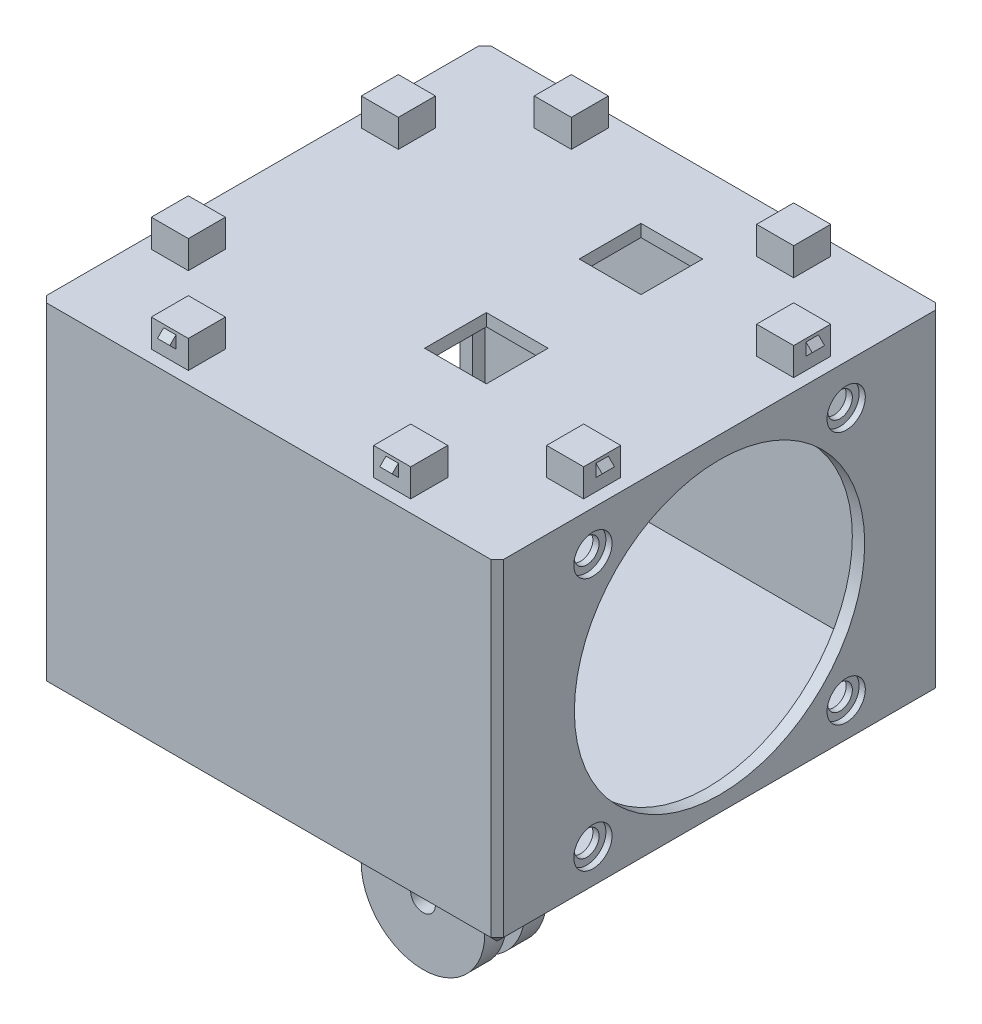
SolidWorks part; units mm, degrees
ref_plane "前视基准面" through (0, 0, 0) normal (0, 0, 1) x (1, 0, 0)
ref_plane "上视基准面" through (0, 0, 0) normal (0, 1, 0) x (1, 0, 0)
ref_plane "右视基准面" through (0, 0, 0) normal (1, 0, 0) x (0, 0, -1)
sketch "草图1" plane through (0, 0, 0) normal (0, 1, 0) x (1, 0, 0)
  line L1 (-65.7153, 32.1762) -> (8.2847, 32.1762)
  line L2 (-65.7153, 32.1762) -> (-65.7153, -39.8238)
  line L3 (-65.7153, -39.8238) -> (8.2847, -39.8238)
  line L4 (8.2847, 32.1762) -> (8.2847, -39.8238)
  dimension "D1" = 74
  dimension "D5" = 72
extrude "凸台-拉伸1" add sketch "草图1" along normal blind 54
sketch "草图2" plane through (0, 54, 0) normal (0, 1, 0) x (1, 0, 0)
  line L0 (8.2847, -39.8238) -> (8.2847, 32.1762) construction
  line L1 (6.2847, 30.1762) -> (-63.7153, 30.1762)
  line L2 (6.2847, 30.1762) -> (6.2847, -37.8238)
  line L3 (6.2847, -37.8238) -> (-63.7153, -37.8238)
  line L4 (-63.7153, 30.1762) -> (-63.7153, -37.8238)
  line L5 (-65.7153, -39.8238) -> (8.2847, -39.8238) construction
  line L6 (8.2847, 32.1762) -> (-65.7153, 32.1762) construction
  line L7 (-65.7153, 32.1762) -> (-65.7153, -39.8238) construction
  dimension "D1" = 2
  dimension "D2" = 2
  dimension "D3" = 2
  dimension "D4" = 2
extrude "切除-拉伸1" cut sketch "草图2" against normal blind 52
sketch "草图4" plane through (8.2847, 0, 0) normal (1, 0, 0) x (0, 0, -1)
  line L1 (32.1762, 54) -> (32.1762, 0) construction
  line L2 (-39.8238, 0) -> (32.1762, 0) construction
  circle A0 centre (-3.8238, 27) radius 23.5
  circle A1 centre (16.6762, 6.5) radius 2
  circle A2 centre (-24.3238, 47.5) radius 2
  circle A3 centre (-24.3238, 6.5) radius 2
  circle A4 centre (16.6762, 47.5) radius 2
  dimension "D1" = 47
  dimension "D2" = 20.5
  dimension "D8" = 4
  dimension "D3" = 20.5
  dimension "D4" = 20.5
  dimension "D5" = 20.5
  dimension "D6" = 36
  dimension "D7" = 27
extrude "切除-拉伸2" cut sketch "草图4" against normal blind 2
sketch "草图5" plane through (0, 0, 0) normal (0, -1, 0) x (1, 0, 0)
  line L0 (-65.7153, -32.1762) -> (-65.7153, 39.8238) construction
  line L1 (-63.7153, 37.8238) -> (-49.7153, 37.8238)
  line L2 (-63.7153, 37.8238) -> (-63.7153, -30.1762)
  line L3 (-63.7153, -30.1762) -> (-49.7153, -30.1762)
  line L4 (-49.7153, 37.8238) -> (-49.7153, -30.1762)
  line L5 (-65.7153, 39.8238) -> (8.2847, 39.8238) construction
  line L6 (8.2847, -32.1762) -> (-65.7153, -32.1762) construction
  dimension "D1" = 2
  dimension "D2" = 2
  dimension "D3" = 2
  dimension "D4" = 14
extrude "切除-拉伸3" cut sketch "草图5" against normal blind 2
sketch "草图6" plane through (0, 0, 37.8238) normal (0, 0, -1) x (-1, 0, 0)
  line L0 (63.7153, 54) -> (-6.2847, 54) construction
  line L1 (63.7153, 52) -> (54.7153, 52)
  line L2 (63.7153, 52) -> (63.7153, 54)
  line L3 (63.7153, 54) -> (54.7153, 54)
  line L4 (54.7153, 52) -> (54.7153, 54)
  line L9 (63.7153, 0) -> (63.7153, 54) construction
  dimension "D1" = 9
  dimension "D2" = 2
  dimension "D3" = 0
  dimension "D4" = 0
sketch "草图7" plane through (0, 0, -30.1762) normal (0, 0, 1) x (1, 0, 0)
  line L0 (-54.7153, 52) -> (-54.7153, 54) construction
  line L1 (-63.7153, 54) -> (-54.7153, 54)
  line L2 (-63.7153, 54) -> (-63.7153, 52)
  line L3 (-63.7153, 52) -> (-54.7153, 52)
  line L4 (-54.7153, 54) -> (-54.7153, 52)
  line L5 (-63.7153, 54) -> (-54.7153, 54) construction
  line L6 (6.2847, 54) -> (-63.7153, 54) construction
  line L7 (-63.7153, 0) -> (-63.7153, 54) construction
  point P12 (-63.7153, 53)
  dimension "D1" = 0
extrude "凸台-拉伸2" add sketch "草图6" along normal blind 5
extrude "凸台-拉伸3" add sketch "草图7" along normal blind 5
sketch "草图9" plane through (-65.7153, 0, 0) normal (-1, 0, 0) x (0, 0, 1)
  line L0 (39.8238, 54) -> (39.8238, 0) construction
  line L1 (35.8238, 50) -> (-28.1762, 50)
  line L2 (35.8238, 50) -> (35.8238, 4)
  line L3 (35.8238, 4) -> (-28.1762, 4)
  line L4 (-28.1762, 50) -> (-28.1762, 4)
  line L5 (-32.1762, 0) -> (39.8238, 0) construction
  line L6 (-32.1762, 54) -> (39.8238, 54) construction
  line L7 (-32.1762, 54) -> (-32.1762, 0) construction
  dimension "D1" = 4
  dimension "D2" = 4
  dimension "D3" = 4
  dimension "D4" = 4
extrude "切除-拉伸4" cut sketch "草图9" against normal up to next
sketch "草图10" plane through (0, 0, 37.8238) normal (0, 0, -1) x (-1, 0, 0)
  line L0 (49.7153, 2) -> (-6.2847, 2) construction
  line L9 (49.7153, 10) -> (45.7153, 10)
  line L10 (49.7153, 10) -> (49.7153, 18)
  line L11 (49.7153, 18) -> (45.7153, 18)
  line L12 (45.7153, 10) -> (45.7153, 18)
  line L13 (49.7153, 25) -> (49.7153, 33)
  line L14 (49.7153, 25) -> (45.7153, 25)
  line L15 (45.7153, 25) -> (45.7153, 33)
  line L16 (49.7153, 33) -> (45.7153, 33)
  line L17 (49.7153, 40) -> (49.7153, 48)
  line L18 (49.7153, 40) -> (45.7153, 40)
  line L19 (45.7153, 40) -> (45.7153, 48)
  line L20 (49.7153, 48) -> (45.7153, 48)
  line L21 (49.7153, 2) -> (49.7153, 0) construction
  point P0 (47.7153, 10)
  dimension "D1" = 4
  dimension "D2" = 8
  dimension "D3" = 8
  dimension "D4" = 3
extrude "凸台-拉伸5" add sketch "草图10" along normal blind 5
sketch "草图11" plane through (0, 0, -30.1762) normal (0, 0, 1) x (1, 0, 0)
  line L0 (6.2847, 2) -> (-49.7153, 2) construction
  line L1 (-45.7153, 10) -> (-49.7153, 10)
  line L2 (-45.7153, 10) -> (-45.7153, 18)
  line L3 (-45.7153, 18) -> (-49.7153, 18)
  line L4 (-49.7153, 10) -> (-49.7153, 18)
  line L5 (-45.7153, 25) -> (-45.7153, 33)
  line L6 (-45.7153, 25) -> (-49.7153, 25)
  line L7 (-49.7153, 25) -> (-49.7153, 33)
  line L8 (-45.7153, 33) -> (-49.7153, 33)
  line L9 (-45.7153, 40) -> (-45.7153, 48)
  line L10 (-45.7153, 40) -> (-49.7153, 40)
  line L11 (-49.7153, 40) -> (-49.7153, 48)
  line L12 (-45.7153, 48) -> (-49.7153, 48)
  line L13 (-49.7153, 2) -> (-49.7153, 0) construction
  dimension "D1" = 4
  dimension "D2" = 8
  dimension "D3" = 8
  dimension "D4" = 3
extrude "凸台-拉伸6" add sketch "草图11" along normal blind 5
sketch "草图15" plane through (0, 54, 0) normal (0, 1, 0) x (1, 0, 0)
  line L0 (6.2847, -37.8238) -> (6.2847, 30.1762) construction
  line L1 (-63.7153, 30.1762) -> (6.2847, 30.1762)
  line L2 (-63.7153, 30.1762) -> (-63.7153, -37.8238)
  line L3 (-63.7153, -37.8238) -> (6.2847, -37.8238)
  line L4 (6.2847, 30.1762) -> (6.2847, -37.8238)
  line L5 (-63.7153, 25.1762) -> (-63.7153, -32.8238) construction
extrude "凸台-拉伸7" add sketch "草图15" against normal blind 2
sketch "草图16" plane through (0, 54, 0) normal (0, 1, 0) x (1, 0, 0)
  line L0 (-43.7153, -31.8238) -> (-49.7153, -31.8238)
  line L1 (-57.7153, 16.1762) -> (-63.7153, 16.1762)
  line L2 (-57.7153, 16.1762) -> (-57.7153, 10.1762)
  line L3 (-57.7153, 10.1762) -> (-63.7153, 10.1762)
  line L4 (-63.7153, 16.1762) -> (-63.7153, 10.1762)
  line L5 (-43.7153, -31.8238) -> (-43.7153, -37.8238)
  line L6 (-43.7153, -37.8238) -> (-49.7153, -37.8238)
  line L7 (-49.7153, -31.8238) -> (-49.7153, -37.8238)
  line L8 (-7.7153, -31.8238) -> (-13.7153, -31.8238)
  line L9 (-7.7153, -31.8238) -> (-7.7153, -37.8238)
  line L10 (-7.7153, -37.8238) -> (-13.7153, -37.8238)
  line L11 (-13.7153, -31.8238) -> (-13.7153, -37.8238)
  line L12 (-43.7153, 30.1762) -> (-49.7153, 30.1762)
  line L13 (-43.7153, 30.1762) -> (-43.7153, 24.1762)
  line L14 (-43.7153, 24.1762) -> (-49.7153, 24.1762)
  line L15 (-49.7153, 30.1762) -> (-49.7153, 24.1762)
  line L16 (-7.7153, 30.1762) -> (-13.7153, 30.1762)
  line L17 (-7.7153, 30.1762) -> (-7.7153, 24.1762)
  line L18 (-7.7153, 24.1762) -> (-13.7153, 24.1762)
  line L19 (-13.7153, 30.1762) -> (-13.7153, 24.1762)
  line L20 (6.2847, 16.1762) -> (0.2847, 16.1762)
  line L21 (6.2847, 16.1762) -> (6.2847, 10.1762)
  line L22 (6.2847, 10.1762) -> (0.2847, 10.1762)
  line L23 (0.2847, 16.1762) -> (0.2847, 10.1762)
  line L24 (6.2847, -17.8238) -> (0.2847, -17.8238)
  line L25 (6.2847, -17.8238) -> (6.2847, -23.8238)
  line L26 (6.2847, -23.8238) -> (0.2847, -23.8238)
  line L27 (0.2847, -17.8238) -> (0.2847, -23.8238)
  line L32 (-57.7153, -17.8238) -> (-63.7153, -17.8238)
  line L33 (-57.7153, -17.8238) -> (-57.7153, -23.8238)
  line L34 (-57.7153, -23.8238) -> (-63.7153, -23.8238)
  line L35 (-63.7153, -17.8238) -> (-63.7153, -23.8238)
  line L36 (8.2847, 32.1762) -> (-65.7153, 32.1762) construction
  line L37 (-65.7153, -39.8238) -> (8.2847, -39.8238) construction
  line L38 (-65.7153, 32.1762) -> (-65.7153, -39.8238) construction
  line L39 (8.2847, -39.8238) -> (8.2847, 32.1762) construction
  point P42 (-10.7153, 30.1762)
  dimension "D1" = 16
  dimension "D2" = 16
  dimension "D3" = 16
  dimension "D4" = 16
  dimension "D5" = 16
  dimension "D6" = 16
  dimension "D7" = 16
  dimension "D8" = 16
  dimension "D9" = 6
  dimension "D10" = 2
  dimension "D11" = 2
  dimension "D12" = 2
  dimension "D13" = 2
extrude "凸台-拉伸8" add sketch "草图16" along normal blind 4.5
sketch "草图17" plane through (-63.7153, 0, 0) normal (-1, 0, 0) x (0, 0, 1)
  line L1 (-14.1762, 58) -> (-12.1762, 58)
  line L2 (-14.1762, 58) -> (-14.1762, 56)
  line L3 (-14.1762, 56) -> (-12.1762, 56)
  line L4 (-12.1762, 58) -> (-12.1762, 56)
  line L5 (19.8238, 58) -> (21.8238, 58)
  line L6 (19.8238, 58) -> (19.8238, 56)
  line L7 (19.8238, 56) -> (21.8238, 56)
  line L8 (21.8238, 58) -> (21.8238, 56)
  line L9 (17.8238, 54) -> (23.8238, 54) construction
  line L10 (23.8238, 58.5) -> (23.8238, 54) construction
  line L11 (-10.1762, 58.5) -> (-10.1762, 54) construction
  dimension "D1" = 2
  dimension "D2" = 2
  dimension "D3" = 2
  dimension "D4" = 2
extrude "凸台-拉伸9" add sketch "草图17" along normal blind 1
sketch "草图18" plane through (0, 0, 37.8238) normal (0, 0, 1) x (1, 0, 0)
  line L0 (-13.7153, 54) -> (-7.7153, 54) construction
  line L1 (-9.7153, 56) -> (-11.7153, 56)
  line L2 (-9.7153, 56) -> (-9.7153, 58)
  line L3 (-9.7153, 58) -> (-11.7153, 58)
  line L4 (-11.7153, 56) -> (-11.7153, 58)
  line L5 (-45.7153, 56) -> (-47.7153, 56)
  line L6 (-45.7153, 56) -> (-45.7153, 58)
  line L7 (-45.7153, 58) -> (-47.7153, 58)
  line L8 (-47.7153, 56) -> (-47.7153, 58)
  line L9 (-7.7153, 58.5) -> (-7.7153, 54) construction
  line L10 (-43.7153, 58.5) -> (-43.7153, 54) construction
  point P11 (-9.7153, 57)
  dimension "D1" = 2
  dimension "D2" = 2
  dimension "D3" = 2
  dimension "D4" = 2
extrude "凸台-拉伸10" add sketch "草图18" along normal blind 1
sketch "草图19" plane through (6.2847, 0, 0) normal (1, 0, 0) x (0, 0, -1)
  line L0 (10.1762, 54) -> (16.1762, 54) construction
  line L1 (14.1762, 56) -> (12.1762, 56)
  line L2 (14.1762, 56) -> (14.1762, 58)
  line L3 (14.1762, 58) -> (12.1762, 58)
  line L4 (12.1762, 56) -> (12.1762, 58)
  line L5 (-19.8238, 56) -> (-21.8238, 56)
  line L6 (-19.8238, 56) -> (-19.8238, 58)
  line L7 (-19.8238, 58) -> (-21.8238, 58)
  line L8 (-21.8238, 56) -> (-21.8238, 58)
  line L9 (16.1762, 58.5) -> (16.1762, 54) construction
  line L10 (-17.8238, 58.5) -> (-17.8238, 54) construction
  dimension "D1" = 2
  dimension "D2" = 2
  dimension "D3" = 2
  dimension "D4" = 2
extrude "凸台-拉伸11" add sketch "草图19" along normal blind 1
sketch "草图20" plane through (0, 0, -30.1762) normal (0, 0, -1) x (-1, 0, 0)
  line L1 (47.7153, 56) -> (45.7153, 56)
  line L2 (47.7153, 56) -> (47.7153, 58)
  line L3 (47.7153, 58) -> (45.7153, 58)
  line L4 (45.7153, 56) -> (45.7153, 58)
  line L5 (11.7153, 56) -> (9.7153, 56)
  line L6 (11.7153, 56) -> (11.7153, 58)
  line L7 (11.7153, 58) -> (9.7153, 58)
  line L8 (9.7153, 56) -> (9.7153, 58)
  line L9 (43.7153, 54) -> (49.7153, 54) construction
  line L10 (49.7153, 58.5) -> (49.7153, 54) construction
  line L11 (13.7153, 58.5) -> (13.7153, 54) construction
  dimension "D1" = 2
  dimension "D2" = 2
  dimension "D3" = 2
  dimension "D4" = 2
extrude "凸台-拉伸12" add sketch "草图20" along normal blind 1
sketch "草图21" plane through (0, 52, 0) normal (0, -1, 0) x (-1, 0, 0)
  line L0 (-6.2847, -37.8238) -> (-6.2847, 30.1762) construction
  line L1 (17.7153, -15.5749) -> (27.7153, -15.5749)
  line L2 (17.7153, -15.5749) -> (17.7153, -5.5749)
  line L3 (17.7153, -5.5749) -> (27.7153, -5.5749)
  line L4 (27.7153, -15.5749) -> (27.7153, -5.5749)
  line L5 (17.7153, 9.4542) -> (27.7153, 9.4542)
  line L6 (17.7153, 9.4542) -> (17.7153, 19.4542)
  line L7 (17.7153, 19.4542) -> (27.7153, 19.4542)
  line L8 (27.7153, 9.4542) -> (27.7153, 19.4542)
  dimension "D1" = 10
  dimension "D2" = 24
extrude "切除-拉伸5" cut sketch "草图21" against normal up to next
sketch "草图25" plane through (0, 0, 0) normal (0, -1, 0) x (1, 0, 0)
  line L0 (8.2847, 39.8238) -> (8.2847, -32.1762) construction
  line L1 (-24.7278, 8.8238) -> (-44.7278, 8.8238)
  line L2 (-24.7278, 8.8238) -> (-24.7278, -1.1762)
  line L3 (-24.7278, -1.1762) -> (-44.7278, -1.1762)
  line L4 (-44.7278, 8.8238) -> (-44.7278, -1.1762)
  point P6 (8.2847, 3.8238)
  point P7 (-24.7278, 3.8238)
  dimension "D1" = 20
  dimension "D2" = 10
extrude "凸台-拉伸15" add sketch "草图25" along normal blind 30
sketch "草图26" plane through (0, 0, 8.8238) normal (0, 0, 1) x (1, 0, 0)
  line L0 (-24.7278, -30) -> (-44.7278, -30) construction
  circle A0 centre (-34.7278, -30) radius 10
extrude "凸台-拉伸16" add sketch "草图26" against normal blind 10
sketch "草图27" plane through (0, 0, 8.8238) normal (0, 0, 1) x (1, 0, 0)
  circle A0 centre (-34.7278, -30) radius 2
  arc A1 (-44.7278, -30) -> (-24.7278, -30) centre (-34.7278, -30) ccw construction
  dimension "D1" = 4
extrude "切除-拉伸6" cut sketch "草图27" against normal blind 10
sketch "草图29" plane through (-44.7278, 0, 0) normal (-1, 0, 0) x (0, 0, 1)
  line L1 (5.3238, -40) -> (2.3238, -40)
  line L2 (5.3238, -40) -> (5.3238, -13)
  line L3 (5.3238, -13) -> (2.3238, -13)
  line L4 (2.3238, -40) -> (2.3238, -13)
  line L5 (8.8238, 0) -> (-1.1762, 0) construction
  point P7 (3.8238, 0)
  point P8 (3.8238, -13)
  dimension "D1" = 3
  dimension "D2" = 27
extrude "切除-拉伸7" cut sketch "草图29" against normal up to next
sketch "草图30" plane through (0, -13, 0) normal (0, -1, 0) x (1, 0, 0)
  line L0 (-24.7278, 5.3238) -> (-44.7278, 5.3238) construction
  line L1 (-33.2278, 2.3238) -> (-36.2278, 2.3238)
  line L2 (-33.2278, 2.3238) -> (-33.2278, 5.3238)
  line L3 (-33.2278, 5.3238) -> (-36.2278, 5.3238)
  line L4 (-36.2278, 2.3238) -> (-36.2278, 5.3238)
  line L5 (-24.7278, 2.3238) -> (-44.7278, 2.3238) construction
  point P8 (-34.7278, 2.3238)
  point P9 (-34.7278, 2.3238)
  dimension "D1" = 3
extrude "切除-拉伸8" cut sketch "草图30" against normal up to next
chamfer "倒角1" distance 1 angle 45 8 edges at (-65.7153, 27, 39.8238) (8.2847, 27, 39.8238) (8.2847, 27, -32.1762) (-65.7153, 27, -32.1762) (-28.7153, 0, 39.8238) (-65.7153, 0, 3.8238) (-28.7153, 0, -32.1762) (8.2847, 0, 3.8238)
chamfer "倒角2" distance 1 angle 45 8 edges at (7.2847, 58, 20.8238) (7.2847, 58, -13.1762) (-10.7153, 58, -31.1762) (-46.7153, 58, -31.1762) (-64.7153, 58, -13.1762) (-64.7153, 58, 20.8238) (-10.7153, 58, 38.8238) (-46.7153, 58, 38.8238)
sketch "草图31" plane through (8.2847, 0, 0) normal (1, 0, 0) x (0, 0, -1)
  circle A0 centre (16.6762, 6.5) radius 3.1
  circle A1 centre (-24.3238, 6.5) radius 3.1
  circle A2 centre (-24.3238, 47.5) radius 3.1
  circle A3 centre (16.6762, 47.5) radius 3.1
  circle A4 centre (16.6762, 6.5) radius 2 construction
  circle A5 centre (-24.3238, 6.5) radius 2 construction
  circle A6 centre (-24.3238, 47.5) radius 2 construction
  circle A7 centre (16.6762, 47.5) radius 2 construction
  dimension "D1" = 6.2
extrude "切除-拉伸9" cut sketch "草图31" against normal blind 1
chamfer "倒角3" distance 1 angle 45 8 edges at (-64.7153, 56, 20.8238) (-64.7153, 56, -13.1762) (-46.7153, 56, -31.1762) (-10.7153, 56, -31.1762) (7.2847, 56, -13.1762) (7.2847, 56, 20.8238) (-46.7153, 56, 38.8238) (-10.7153, 56, 38.8238)
fillet "圆角1" radius 1 12 edges at (-45.7153, 29, 32.8238) (-45.7153, 14, 32.8238) (-49.7153, 14, 32.8238) (-45.7153, 44, 32.8238) (-49.7153, 44, 32.8238) (-49.7153, 29, 32.8238) (-45.7153, 14, -25.1762) (-45.7153, 29, -25.1762) (-45.7153, 44, -25.1762) (-49.7153, 44, -25.1762) (-49.7153, 29, -25.1762) (-49.7153, 14, -25.1762)
